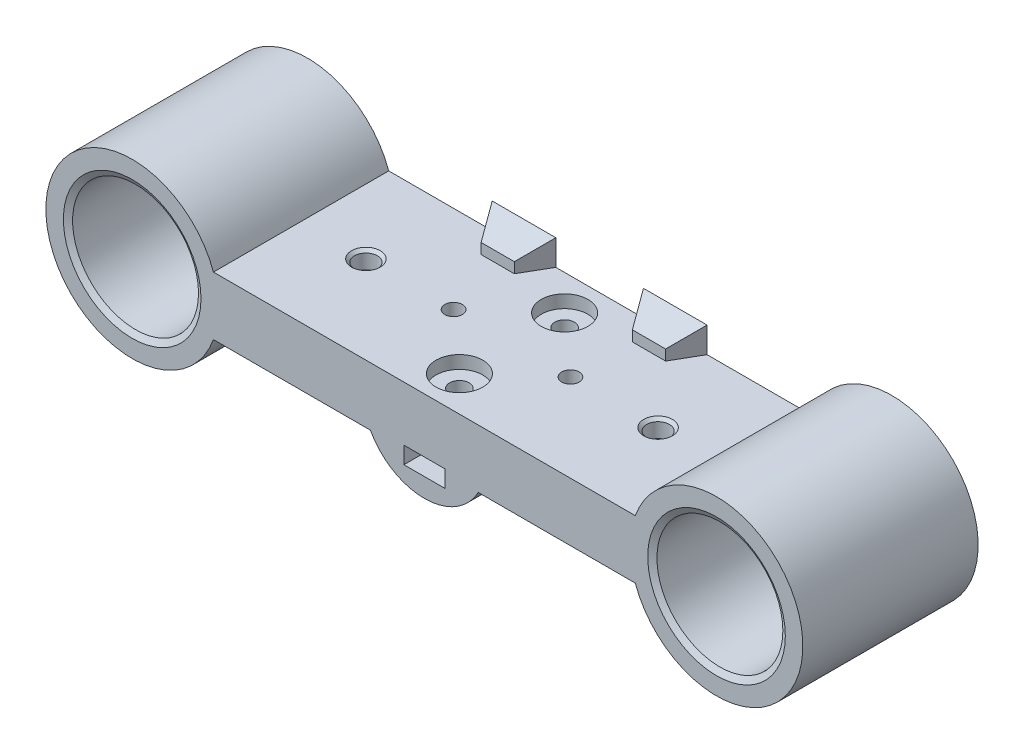
SolidWorks part; units mm, degrees
material "ABS"
ref_plane "Front Plane" through (0, 0, 0) normal (0, 0, 1) x (1, 0, 0)
ref_plane "Top Plane" through (0, 0, 0) normal (0, 1, 0) x (1, 0, 0)
ref_plane "Right Plane" through (0, 0, 0) normal (1, 0, 0) x (0, 0, -1)
sketch "Sketch1" plane through (0, 0, 0) normal (0, 0, 1) x (1, 0, 0)
  line L0 (-50, 0) -> (50, 0) construction
  line L1 (0, 0) -> (0, 5.35) construction
  line L2 (-33.0913, 2.425) -> (-33.0913, 0) construction
  line L3 (-33.0913, 0) -> (-33.0913, -2.425) construction
  line L4 (33.0731, 2.425) -> (33.0731, 0) construction
  line L5 (33.0731, 0) -> (33.0731, -2.425) construction
  line L7 (-33.0913, 2.425) -> (33.0731, 2.425)
  line L8 (12.362, -2.425) -> (33.0731, -2.425)
  line L9 (-3.5, -7.25) -> (3.5, -7.25)
  line L10 (-3.5, -7.25) -> (-3.5, -5.35)
  line L11 (-3.5, -5.35) -> (3.5, -5.35)
  line L12 (3.5, -7.25) -> (3.5, -5.35)
  line L13 (-33.0913, -2.425) -> (-12.3457, -2.425)
  circle A0 centre (50, 0) radius 10.775
  arc A1 (35.93, -4.5094) -> (35.93, 4.5094) centre (50, 0) ccw
  circle A3 centre (50, 0) radius 14.775 construction
  arc A5 (-35.9253, -4.4949) -> (-35.9253, 4.4949) centre (-50, 0) cw
  circle A6 centre (-50, 0) radius 10.775
  circle A7 centre (0, 0) radius 5.35 construction
  arc A8 (-9.62, -4.2078) -> (9.6149, -4.2194) centre (0, 0) ccw
  arc A12 (33.0731, 2.425) -> (35.93, 4.5094) centre (33.0731, 5.425) ccw
  arc A13 (33.0731, -2.425) -> (35.93, -4.5094) centre (33.0731, -5.425) cw
  arc A14 (9.6149, -4.2194) -> (12.362, -2.425) centre (12.362, -5.425) cw
  arc A17 (-9.62, -4.2078) -> (-12.3457, -2.425) centre (-12.3457, -5.4) ccw
  arc A18 (-33.0913, -2.425) -> (-35.9253, -4.4949) centre (-33.0913, -5.4) ccw
  arc A19 (-33.0913, 2.425) -> (-35.9253, 4.4949) centre (-33.0913, 5.4) cw
  point P5 (92.6913, 4.4148)
  point P8 (51.9538, 3.6546)
  point P17 (0, -5.35)
  point P37 (35.4219, -2.4041)
  point P40 (10.2161, -2.425)
  point P41 (78.2511, 0)
  point P50 (-35.4219, -2.4041)
  dimension "D2" = 4
  dimension "D3" = 21.55
  dimension "D5" = 21.55
  dimension "D6" = 21
  dimension "D9" = 3
  dimension "D1" = 100
  dimension "D4" = 7.25
  dimension "D7" = 1.9
  dimension "D8" = 7
extrude "Boss-Extrude1" add sketch "Sketch1" along normal blind 30
sketch3d "3DSketch5"
  line L0 (-50, 0, 0) -> (-50, 0, 30)
  line L1 (-50, 0, 30) -> (-50, 0, 0) construction
  line L2 (-50, 0, 30) -> (-50, 0, 0) construction
  line L3 (50, 0, 22.4) -> (50, 0, 7.6)
  line L4 (50, 0, 30) -> (50, 0, 0) construction
  line L5 (50, 0, 30) -> (50, 0, 0) construction
  line L6 (50, 0, 15) -> (-50, 0, 15) construction
  line L7 (0, 0, 15) -> (25, 0, 15) construction
  line L8 (0, 0, 15) -> (-25, 0, 15) construction
  line L11 (0, 0, 15) -> (0, 7.375, 15) construction
  line L12 (0, 0, 15) -> (0, -7.375, 15) construction
  dimension "D1" = 25
  dimension "D2" = 25
  dimension "D3" = 100
  dimension "D4" = 14.75
ref_plane "Plane2" through (0, 0, 0) normal (0, 1, 0) x (1, 0, 0)
sketch "Sketch32" plane through (0, 0, 0) normal (0, -1, 0) x (1, 0, 0)
  line L0 (12.362, 30) -> (33.0731, 30) construction
  line L1 (-38.6611, 30) -> (7.9887, 30)
  line L2 (-38.6611, 30) -> (-38.6611, 0)
  line L3 (-38.6611, 0) -> (7.9887, 0)
  line L5 (7.9887, 30) -> (38.7521, 30)
  line L7 (7.9887, 0) -> (38.7521, 0)
  line L8 (38.7521, 30) -> (38.7521, 0)
  line L9 (12.362, 0) -> (33.0731, 0) construction
  line L10 (-33.0913, 0) -> (-12.3457, 0) construction
extrude "Boss-Extrude4" add sketch "Sketch32" along normal blind 5 and the other way blind 5
sketch "Sketch30" plane through (0, -5.35, 0) normal (0, 1, 0) x (1, 0, 0)
  line L1 (3.5, 0) -> (-3.5, 0) construction
  line L2 (3.5, -30) -> (-3.5, -30) construction
  circle A0 centre (0, -6) radius 1.675
  circle A1 centre (0, -24) radius 1.675
  dimension "D1" = 3.35
  dimension "D2" = 6
  dimension "D3" = 6
extrude "Cut-Extrude14" cut sketch "Sketch30" along normal through all
sketch "Sketch31" plane through (0, 5, 0) normal (0, 1, 0) x (1, 0, 0)
  circle A0 centre (0, -6) radius 4
  circle A1 centre (0, -24) radius 4
  dimension "D1" = 8
extrude "Cut-Extrude15" cut sketch "Sketch31" against normal blind 2.2
chamfer "Chamfer1" distance 1 angle 45 2 edges at (0, -5.35, 30) (0, -5.35, 0)
ref_plane "Plane1" through (0, 0, 0) normal (1, 0, 0) x (0, 0, -1)
sketch "Sketch42" plane through (0, 0, 0) normal (0, 0, -1) x (-1, 0, 0)
  line L0 (-7.5, 2.1624) -> (0, 2.1624) construction
  line L1 (-7.5, 2.1624) -> (-18.3856, 2.1624)
  line L2 (-7.5, 2.1624) -> (-7.5, 9.3946)
  line L3 (-7.5, 9.3946) -> (-18.3856, 9.3946)
  line L4 (-18.3856, 2.1624) -> (-18.3856, 9.3946)
  line L5 (18.3856, 2.1624) -> (7.5, 2.1624)
  line L6 (18.3856, 2.1624) -> (18.3856, 9.3946)
  line L7 (18.3856, 9.3946) -> (7.5, 9.3946)
  line L8 (7.5, 2.1624) -> (7.5, 9.3946)
  line L9 (0, 2.1624) -> (7.5, 2.1624) construction
  line L10 (0, 0) -> (0, 2.1624) construction
  dimension "D1" = 15
extrude "Boss-Extrude6" add sketch "Sketch42" against normal blind 4.5 draft 30
sketch "Sketch43" plane through (0, 0, 0) normal (0, 1, 0) x (1, 0, 0)
  line L0 (0, -15) -> (-25, -15) construction
  line L1 (50, -15) -> (-50, -15) construction
  line L2 (0, -15) -> (25, -15) construction
  circle A0 centre (25, -15) radius 1.95
  circle A1 centre (-25, -15) radius 1.95
  circle A2 centre (10, -15) radius 1.5
  circle A3 centre (-10, -15) radius 1.5
  dimension "D2" = 3.9
  dimension "D3" = 3.9
  dimension "D4" = 3
  dimension "D1" = 25
  dimension "D5" = 10
  dimension "D6" = 10
extrude "Cut-Extrude16" cut sketch "Sketch43" against normal through all and the other way through all
chamfer "Chamfer2" distance 0.5 angle 45 2 edges at (25, 5, 13.05) (-25, 5, 13.05)
chamfer "Chamfer3" distance 1 angle 30 4 edges at (-60.775, 0, 30) (60.775, 0, 30) (60.775, 0, 0) (-60.775, 0, 0) first distance on face at (0, -2.5833, 30) first distance on face at (60.775, 0, 30) first distance on face at (-60.775, 0, 30)
sketch "Sketch44" plane through (0, -5, 0) normal (0, -1, 0) x (1, 0, 0)
  circle A0 centre (25, 15) radius 5.5
  circle A1 centre (-25, 15) radius 5.5
  dimension "D1" = 11
extrude "Cut-Extrude17" cut sketch "Sketch44" against normal blind 7
